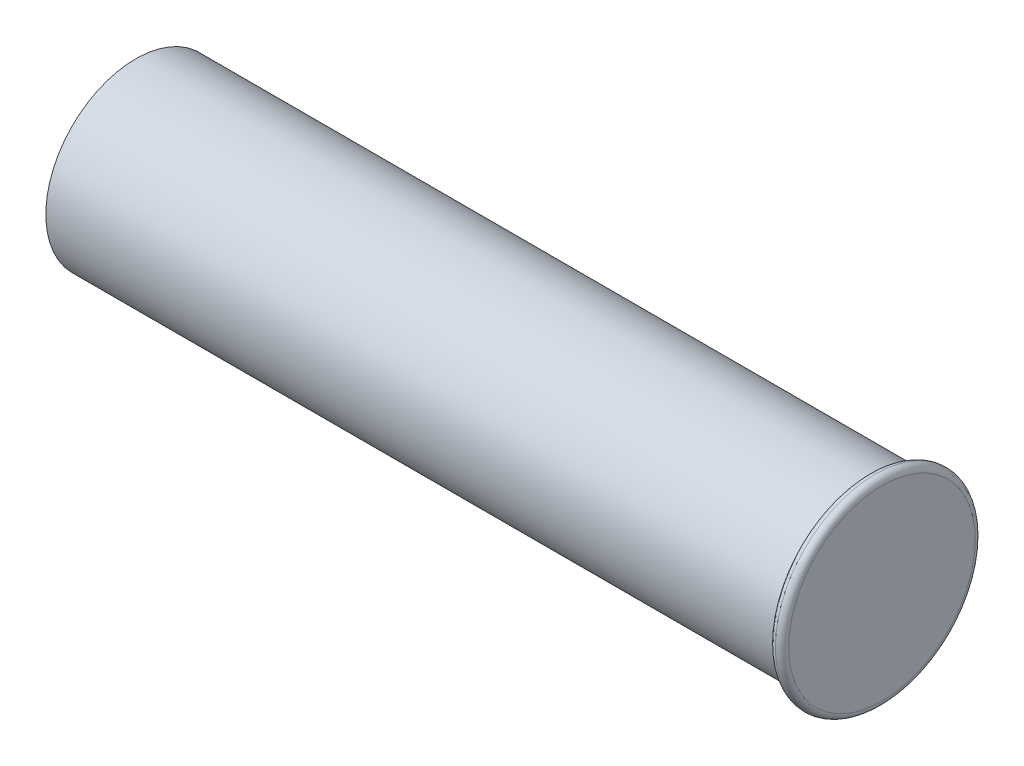
SolidWorks part; units mm, degrees
material "Rubber"
ref_plane "Front Plane" through (0, 0, 0) normal (0, 0, 1) x (1, 0, 0)
ref_plane "Top Plane" through (0, 0, 0) normal (0, 1, 0) x (1, 0, 0)
ref_plane "Right Plane" through (0, 0, 0) normal (1, 0, 0) x (0, 0, -1)
sketch "Sketch1" plane through (0, 0, 0) normal (1, 0, 0) x (0, 0, -1)
  circle A0 centre (0, 0) radius 12.5
  circle A1 centre (0, 0) radius 13.5
  dimension "D1" = 25
  dimension "D2" = 27
extrude "Boss-Extrude5" add sketch "Sketch1" along normal blind 110
sketch "Sketch4" plane through (110, 0, 0) normal (1, 0, 0) x (0, 0, -1)
  circle A0 centre (0, 0) radius 15
  dimension "D1" = 30
extrude "Boss-Extrude6" add sketch "Sketch4" along normal blind 2
fillet "Fillet7" radius 1 2 edges at (110, 0, -15) (112, 0, -15)
